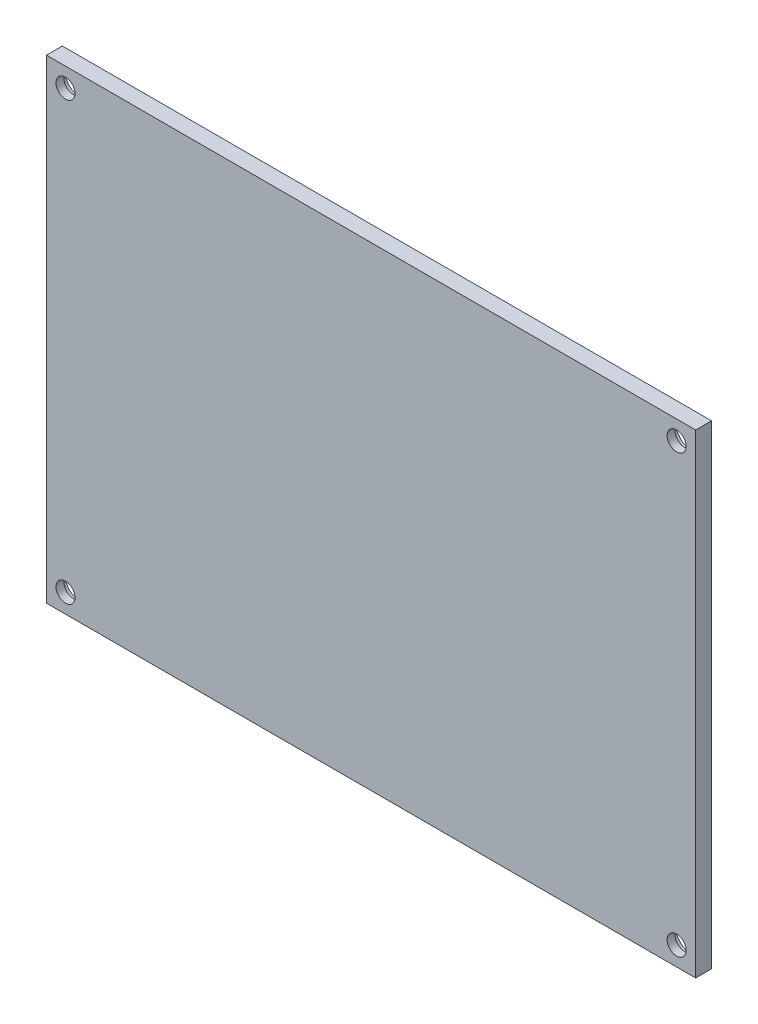
SolidWorks part; units mm, degrees
ref_plane "Front Plane" through (0, 0, 0) normal (0, 0, 1) x (1, 0, 0)
ref_plane "Top Plane" through (0, 0, 0) normal (0, 1, 0) x (1, 0, 0)
ref_plane "Right Plane" through (0, 0, 0) normal (1, 0, 0) x (0, 0, -1)
sketch "Sketch1" plane through (0, 0, 0) normal (0, 0, 1) x (1, 0, 0)
  line L16 (136.4912, -27.2639) -> (136.4912, 32.5361)
  line L17 (54.6912, -27.2639) -> (136.4912, -27.2639)
  line L18 (54.6912, 32.5361) -> (54.6912, -27.2639)
  line L19 (136.4912, 32.5361) -> (54.6912, 32.5361)
  line L20 (136.4912, -27.2639) -> (136.4912, 32.5361)
  line L21 (54.6912, -27.2639) -> (136.4912, -27.2639)
  line L22 (54.6912, 32.5361) -> (54.6912, -27.2639)
  line L23 (136.4912, 32.5361) -> (54.6912, 32.5361)
  dimension "D1" = 0.1
extrude "Boss-Extrude1" add sketch "Sketch1" along normal blind 2
hole_wizard "CBORE for M2 Pan Head Machine Screw1" positions "Sketch4" profile "Sketch3" counterbore size "M2" standard "ANSI Metric"
sketch "Sketch4" plane through (0, 0, 0) normal (0, 0, -1) x (-1, 0, 0)
  point P0 (-134.0912, 30.1361)
  point P3 (-57.0912, 30.1361)
  point P6 (-57.0912, -24.8639)
  point P9 (-134.0912, -24.8639)
sketch "Sketch3" plane through (134.0912, 30.1361, 0) normal (1, 0, 0) x (0, 1, 0)
  line L0 (0, 0) -> (0, 6.721)
  line L1 (0, 6.721) -> (1.2, 6)
  line L2 (1.2, 6) -> (1.2, 1)
  line L3 (1.2, 1) -> (2.125, 1)
  line L4 (2.125, 1) -> (2.125, 0)
  line L5 (2.125, 0) -> (0, 0)
  line L10 (0, 6.721) -> (-1.2, 6) construction
  line L11 (0, -6.35) -> (0, 107.95) construction
  dimension "Hole Dia." = 2.4
  dimension "Hole Depth" = 6
  dimension "C'Bore Dia." = 4.25
  dimension "C'Bore Depth" = 1
  dimension "Drill Angle" = 118
